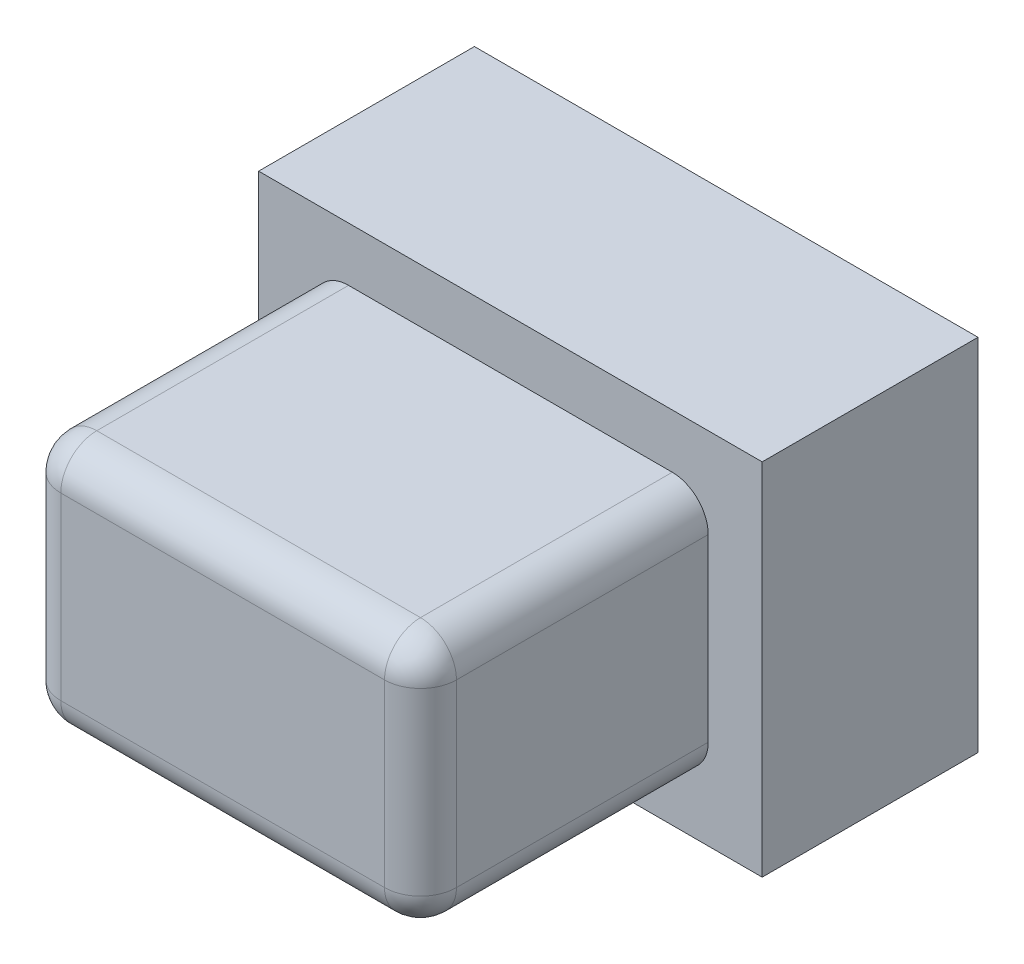
SolidWorks part; units mm, degrees
ref_plane "前视基准面" through (0, 0, 0) normal (0, 0, 1) x (1, 0, 0)
ref_plane "上视基准面" through (0, 0, 0) normal (0, 1, 0) x (1, 0, 0)
ref_plane "右视基准面" through (0, 0, 0) normal (1, 0, 0) x (0, 0, -1)
sketch "草图1" plane through (0, 0, 0) normal (0, 0, 1) x (1, 0, 0)
  line L1 (-3.5, 2.5) -> (3.5, 2.5)
  line L2 (-3.5, 2.5) -> (-3.5, -2.5)
  line L3 (-3.5, -2.5) -> (3.5, -2.5)
  line L4 (3.5, 2.5) -> (3.5, -2.5)
  line L5 (-3.5, 2.5) -> (3.5, -2.5) construction
  line L6 (-3.5, -2.5) -> (3.5, 2.5) construction
  point P0 (0, 0)
  dimension "D1" = 7
  dimension "D2" = 5
extrude "凸台-拉伸1" add sketch "草图1" along normal blind 3
sketch "草图2" plane through (0, 0, 3) normal (0, 0, 1) x (1, 0, 0)
  line L1 (-2.75, 1.75) -> (2.75, 1.75)
  line L2 (-2.75, 1.75) -> (-2.75, -1.75)
  line L3 (-2.75, -1.75) -> (2.75, -1.75)
  line L4 (2.75, 1.75) -> (2.75, -1.75)
  line L5 (-2.75, 1.75) -> (2.75, -1.75) construction
  line L6 (-2.75, -1.75) -> (2.75, 1.75) construction
  point P0 (0, 0)
  dimension "D1" = 5.5
  dimension "D2" = 3.5
extrude "凸台-拉伸2" add sketch "草图2" along normal blind 4
fillet "圆角1" radius 0.5 4 edges at (0, -1.75, 7) (-2.75, 0, 7) (0, 1.75, 7) (2.75, 0, 7)
fillet "圆角2" radius 0.5 8 edges at (2.6036, 1.6036, 6.8536) (2.6036, -1.6036, 6.8536) (-2.6036, -1.6036, 6.8536) (-2.6036, 1.6036, 6.8536) (2.75, 1.75, 4.75) (2.75, -1.75, 4.75) (-2.75, -1.75, 4.75) (-2.75, 1.75, 4.75)
